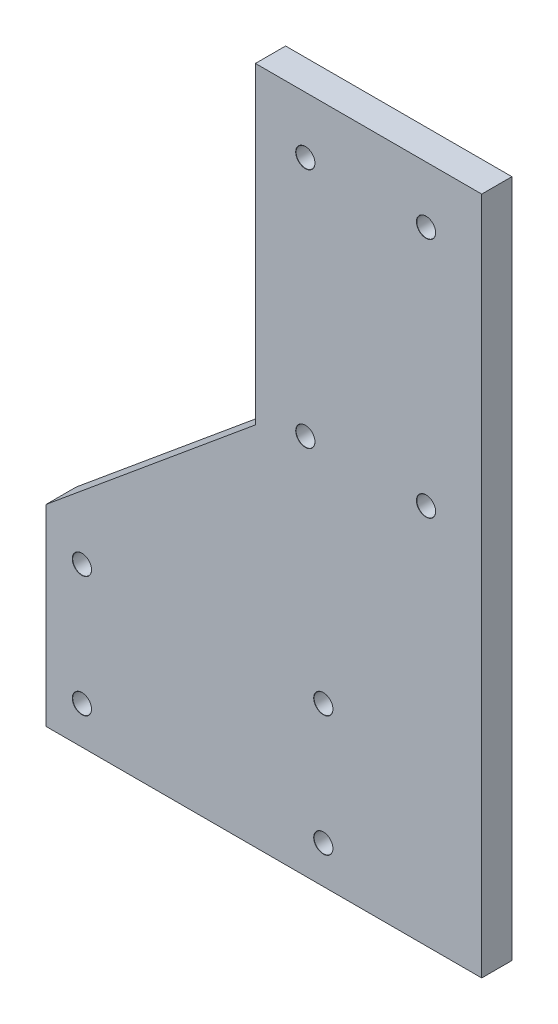
SolidWorks part; units mm, degrees
ref_plane "前视基准面" through (0, 0, 0) normal (0, 0, 1) x (1, 0, 0)
ref_plane "上视基准面" through (0, 0, 0) normal (0, 1, 0) x (1, 0, 0)
ref_plane "右视基准面" through (0, 0, 0) normal (1, 0, 0) x (0, 0, -1)
sketch "草图1" plane through (0, 0, 0) normal (0, 0, 1) x (1, 0, 0)
  line L0 (0, 0) -> (-41.5, 0)
  line L1 (-41.5, 0) -> (-41.5, 25.5)
  line L2 (-41.5, 25.5) -> (-13.75, 48.5)
  line L6 (14.05, -11.5) -> (-49.0563, -11.5) construction
  line L7 (-13.75, 48.5) -> (-13.75, 90)
  line L8 (-13.75, 90) -> (16.25, 90)
  line L9 (16.25, 90) -> (16.25, 0)
  line L10 (-92.1756, 35) -> (57.8057, 35) construction
  line L11 (-105.9645, 43.75) -> (59.2906, 43.75) construction
  line L12 (1.25, -9) -> (1.25, 87.7198) construction
  line L13 (0, 0) -> (16.25, 0)
  dimension "D1" = 41.5
  dimension "D2" = 90
  dimension "D3" = 25.5
  dimension "D4" = 30
  dimension "D5" = 41.5
  dimension "D6" = 35
  dimension "D7" = 8.75
extrude "凸台-拉伸1" add sketch "草图1" along normal blind 4
hole_wizard "Ø2.5mm 暗销孔1" positions "草图2" profile "草图3" hole size "Ø2.5" standard "ISO" end condition through all
sketch "草图2" plane through (0, 0, 4) normal (0, 0, 1) x (1, 0, 0)
  line L0 (-20.75, 0) -> (-20.75, 28.9161) construction
  line L1 (-41.5, 0) -> (16.25, 0) construction
  line L2 (-36.75, 21) -> (-4.75, 21) construction
  line L3 (1.25, 90) -> (1.25, 32.5659) construction
  line L6 (8.8664, 82.5) -> (-7.1336, 82.5) construction
  line L7 (-7.1336, 82.5) -> (-7.1336, 50.5) construction
  line L8 (-7.1336, 50.5) -> (8.8664, 50.5) construction
  line L9 (8.8664, 50.5) -> (8.8664, 82.5) construction
  point P6 (-36.75, 5)
  point P8 (-36.75, 21)
  point P12 (-4.75, 5)
  point P13 (-4.75, 21)
  point P44 (-7.1336, 82.5)
  point P47 (8.8664, 82.5)
  point P51 (-7.1336, 50.5)
  point P54 (8.8664, 50.5)
  point P62 (0, 0)
  dimension "D1" = 16
  dimension "D2" = 16
  dimension "D3" = 0
  dimension "D4" = 5
sketch "草图3" plane through (8.8664, 50.5, 4) normal (1, 0, 0) x (0, -1, 0)
  line L0 (0, 0) -> (0, 4)
  line L1 (0, 4) -> (1.25, 4)
  line L2 (1.25, 4) -> (1.25, 0.025)
  line L3 (1.25, 0.025) -> (1.275, 0)
  line L5 (1.275, 0) -> (0, 0)
  line L6 (-1.25, 0.025) -> (-1.275, 0) construction
  line L11 (0, -6.35) -> (0, 107.95) construction
  dimension "通孔孔直径" = 2.5
  dimension "通孔孔深度" = 4
  dimension "近端锥形沉头孔直径" = 2.55
  dimension "近端锥形沉头孔角度" = 90
